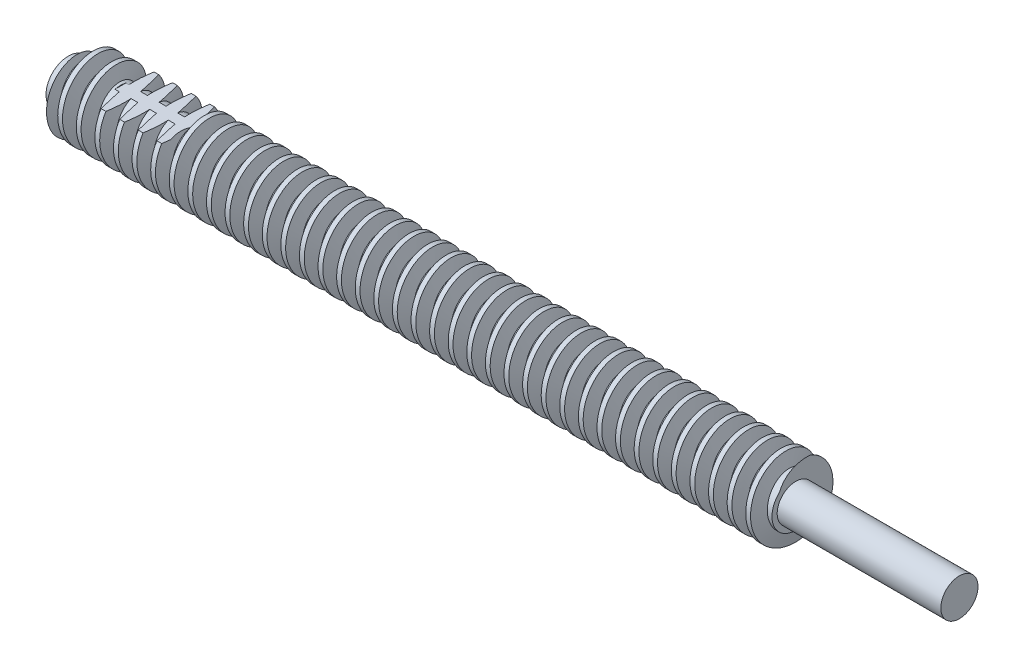
SolidWorks part; units mm, degrees
ref_plane "Front Plane" through (0, 0, 0) normal (0, 0, 1) x (1, 0, 0)
ref_plane "Top Plane" through (0, 0, 0) normal (0, 1, 0) x (1, 0, 0)
ref_plane "Right Plane" through (0, 0, 0) normal (1, 0, 0) x (0, 0, -1)
sketch "Sketch1" plane through (0, 0, 0) normal (0, 0, 1) x (1, 0, 0)
  line L0 (6.35, 0) -> (-97.6665, 0) construction
  line L1 (6.35, 3.175) -> (6.35, 0)
  line L2 (6.35, 3.175) -> (-69.85, 3.175)
  line L3 (-69.85, 3.175) -> (-69.85, 0)
  line L4 (-69.85, 0) -> (6.35, 0)
  dimension "D1" = 6.35
  dimension "D2" = 76.2
  dimension "D3" = 6.35
revolve "Revolve1" add sketch "Sketch1" angle 360 about L0
sketch "Sketch2" plane through (-69.85, 0, 0) normal (-1, 0, 0) x (0, 0, 1)
  circle A0 centre (0, 0) radius 2.6987
  dimension "D1" = 5.3975
curve "Helix/Spiral1" pitch 1.5875 height 63.5 turns 40
sketch "Sketch3" plane through (0, 0, 0) normal (0, 0, 1) x (1, 0, 0)
  line L0 (0, 0) -> (-37.9082, 0) construction
  line L1 (-13.4568, 3.175) -> (-13.1612, 2.032)
  line L2 (6.35, 3.175) -> (-69.85, 3.175) construction
  line L3 (-13.1612, 2.032) -> (-12.5728, 2.032)
  line L4 (-12.867, 2.032) -> (-12.867, 3.175) construction
  line L6 (-13.4568, 3.175) -> (-12.2772, 3.175)
  line L7 (-12.2772, 3.175) -> (-12.5728, 2.032)
  dimension "D1" = 14.5
  dimension "D2" = 6.35
  dimension "D3" = 4.064
  dimension "D4" = 0.2942
sweep "Cut-Sweep1" cut profiles "Sketch3" path "Helix/Spiral1"
sketch "Sketch4" plane through (0, 0, 0) normal (0, 0, 1) x (1, 0, 0)
  line L0 (-71.929, 0.0732) -> (2.5071, 0.0732) construction
  line L1 (-69.215, 1.9782) -> (-69.723, 1.9782)
  line L2 (-69.215, 1.9782) -> (-68.323, 3.5232)
  line L3 (-68.323, 3.5232) -> (-69.85, 3.5232)
  line L4 (-69.723, 1.9782) -> (-69.85, 1.6607)
  line L6 (-69.85, 1.6607) -> (-69.85, 3.5232)
  dimension "D1" = 3.175
revolve "Cut-Revolve1" cut sketch "Sketch4" angle 360 about L0
sketch "Sketch5" plane through (0, 0, 0) normal (0, 0, 1) x (1, 0, 0)
  line L0 (12.7257, 0) -> (-72.8797, 0) construction
  line L1 (6.35, 1.5875) -> (-7.62, 1.5875)
  line L2 (6.35, -3.175) -> (6.35, 3.175) construction
  line L3 (-7.62, 1.5875) -> (-7.62, 4.5095)
  line L4 (-7.62, 4.5095) -> (6.35, 4.5095)
  line L5 (6.35, 4.5095) -> (6.35, 1.5875)
  dimension "D1" = 3.175
  dimension "D2" = 13.97
  dimension "D3" = 2.922
revolve "Cut-Revolve2" [suppressed] cut sketch "Sketch5" angle 360 about L0
sketch "Sketch6" plane through (0, 0, 0) normal (0, 0, 1) x (1, 0, 0)
  line L0 (-69.215, 1.9782) -> (-69.723, 1.9782) construction
  line L1 (-65.278, 1.9782) -> (-59.182, 1.9782)
  line L2 (-65.278, 1.9782) -> (-65.278, 4.0102)
  line L3 (-65.278, 4.0102) -> (-59.182, 4.0102)
  line L4 (-59.182, 1.9782) -> (-59.182, 4.0102)
  line L5 (-65.278, 1.9782) -> (-59.182, 4.0102) construction
  line L6 (-65.278, 4.0102) -> (-59.182, 1.9782) construction
  line L7 (-69.85, 1.6607) -> (-69.85, -1.5143) construction
  point P0 (-62.23, 2.9942)
  dimension "D1" = 0
  dimension "D2" = 2.032
  dimension "D3" = 6.096
  dimension "D4" = 4.572
extrude "Cut-Extrude1" cut sketch "Sketch6" against normal mid plane 12.7
sketch "Sketch7" plane through (6.35, 0, 0) normal (1, 0, 0) x (0, 0, -1)
  circle A0 centre (0, 0) radius 1.5875
  dimension "D1" = 3.175
extrude "Cut-Extrude2" cut sketch "Sketch7" against normal blind 13.97
